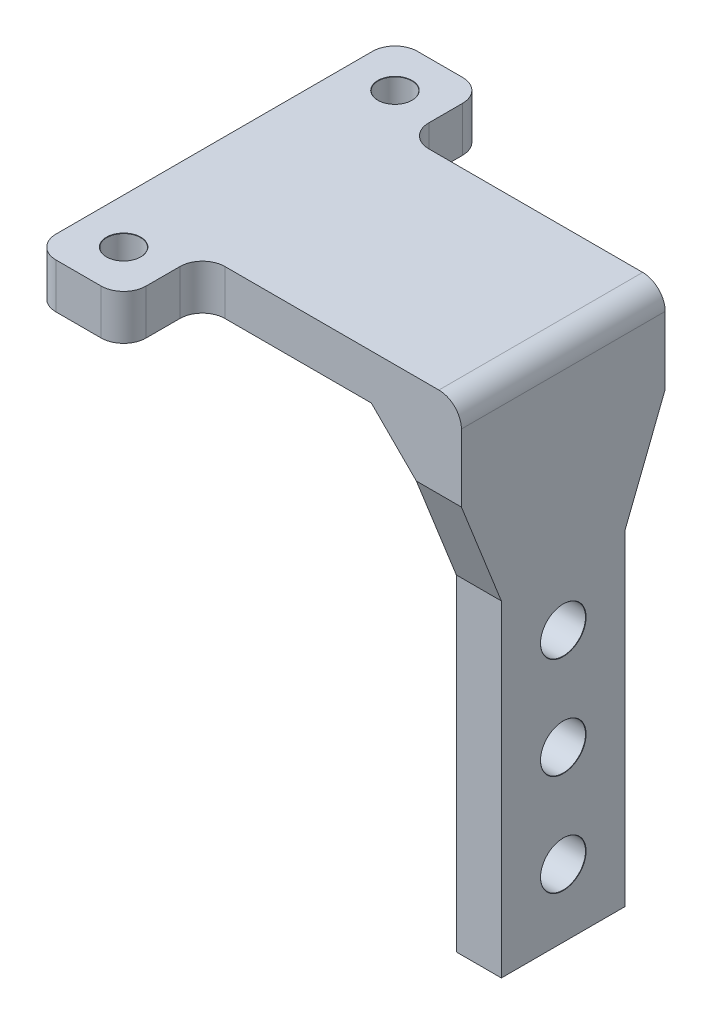
SolidWorks part; units mm, degrees
material "ABS"
ref_plane "Front Plane" through (0, 0, 0) normal (0, 0, 1) x (1, 0, 0)
ref_plane "Top Plane" through (0, 0, 0) normal (0, 1, 0) x (1, 0, 0)
ref_plane "Right Plane" through (0, 0, 0) normal (1, 0, 0) x (0, 0, -1)
sketch "Sketch1" plane through (0, 0, 0) normal (0, 1, 0) x (1, 0, 0)
  line L0 (0, 16.05) -> (0, -16.05)
  line L1 (0, -16.05) -> (8, -16.05)
  line L2 (8, -16.05) -> (8, -9.05)
  line L3 (8, -9.05) -> (31, -9.05)
  line L4 (31, -9.05) -> (31, 9.05)
  line L5 (31, 9.05) -> (8, 9.05)
  line L6 (8, 9.05) -> (8, 16.05)
  line L7 (8, 16.05) -> (0, 16.05)
  dimension "D1" = 32.1
  dimension "D2" = 8
  dimension "D3" = 7
  dimension "D4" = 23
extrude "Boss-Extrude1" add sketch "Sketch1" along normal blind 4
fillet "Fillet1" radius 2 6 edges at (0, 2, -16.05) (8, 2, -9.05) (8, 2, -16.05) (0, 2, 16.05) (8, 2, 16.05) (8, 2, 9.05)
hole_wizard "Ø3.0mm Dowel Hole1" positions "Sketch2" profile "Sketch3" hole size "Ø3.0" standard "ANSI Metric" end condition through all
sketch "Sketch2" plane through (0, 4, 0) normal (0, 1, 0) x (1, 0, 0)
  line L0 (4, 14.9464) -> (4, 9.6271) construction
  line L2 (0, 14.05) -> (0, -14.05) construction
  line L3 (8, 11.05) -> (8, 14.05) construction
  line L4 (6, 16.05) -> (2, 16.05) construction
  line L5 (2, -16.05) -> (6, -16.05) construction
  point P0 (4, 12.05)
  point P2 (4, -12.05)
  dimension "D1" = 4
  dimension "D2" = 4
sketch "Sketch3" plane through (4, 4, -12.05) normal (1, 0, 0) x (0, 0, 1)
  line L0 (0, 0) -> (0, 4)
  line L1 (0, 4) -> (1.5, 4)
  line L2 (1.5, 4) -> (1.5, 0.025)
  line L3 (1.5, 0.025) -> (1.525, 0)
  line L5 (1.525, 0) -> (0, 0)
  line L6 (-1.5, 0.025) -> (-1.525, 0) construction
  line L11 (0, -6.35) -> (0, 107.95) construction
  dimension "Thru Hole Dia." = 3
  dimension "Thru Hole Depth" = 4
  dimension "Near C'Sink Dia." = 3.05
  dimension "Near C'Sink Angle" = 90
sketch "Sketch4" plane through (0, 0, 0) normal (0, -1, 0) x (-1, 0, 0)
  line L0 (-31, 9.05) -> (-10, 9.05) construction
  line L1 (-31, -9.05) -> (-27, -9.05)
  line L2 (-31, -9.05) -> (-31, 9.05)
  line L3 (-31, 9.05) -> (-27, 9.05)
  line L4 (-27, -9.05) -> (-27, 9.05)
  dimension "D1" = 4
extrude "Boss-Extrude2" add sketch "Sketch4" along normal blind 42
chamfer "Chamfer1" distance 4 angle 45 1 edges at (27, 0, 0)
fillet "Fillet2" radius 2 1 edges at (31, 4, 0)
hole_wizard "Ø4.0mm Dowel Hole1" positions "Sketch7" profile "Sketch9" hole size "Ø4.0" standard "ANSI Metric" end condition through all
sketch "Sketch7" plane through (31, 0, 0) normal (1, 0, 0) x (0, 0, -1)
  line L0 (0, -29.3755) -> (0, -38.7068) construction
  line L2 (-9.05, 2) -> (-9.05, -42) construction
  line L3 (9.05, 2) -> (9.05, -42) construction
  line L4 (9.05, -42) -> (-9.05, -42) construction
  point P0 (0, -36)
  point P2 (0, -27)
  point P4 (0, -18)
  dimension "D1" = 6
  dimension "D2" = 9
  dimension "D3" = 9
sketch "Sketch9" plane through (31, -36, 0) normal (0, 1, 0) x (0, 0, -1)
  line L0 (0, 0) -> (0, 31)
  line L1 (0, 31) -> (2, 31)
  line L2 (2, 31) -> (2, 0.025)
  line L3 (2, 0.025) -> (2.025, 0)
  line L5 (2.025, 0) -> (0, 0)
  line L6 (-2, 0.025) -> (-2.025, 0) construction
  line L11 (0, -6.35) -> (0, 107.95) construction
  dimension "Thru Hole Dia." = 4
  dimension "Thru Hole Depth" = 31
  dimension "Near C'Sink Dia." = 4.05
  dimension "Near C'Sink Angle" = 90
sketch "Sketch11" plane through (27, 0, 0) normal (-1, 0, 0) x (0, 0, 1)
  line L0 (-9.05, -4) -> (-5.5, -13)
  line L1 (-5.5, -13) -> (-5.5, -42)
  line L2 (9.05, -42) -> (-9.05, -42) construction
  line L3 (-5.5, -37.5084) -> (-5.5, -13) construction
  line L4 (-5.5, -42) -> (-9.05, -42)
  line L5 (-9.05, -4) -> (-9.05, -42)
  line L7 (9.05, -4) -> (-9.05, -4) construction
  dimension "D1" = 9
extrude "Cut-Extrude1" cut sketch "Sketch11" against normal through all both and the other way through all
sketch "Sketch12" plane through (27, 0, 0) normal (-1, 0, 0) x (0, 0, 1)
  line L0 (9.05, -4) -> (5.5, -13)
  line L1 (5.5, -13) -> (5.5, -42)
  line L2 (9.05, -42) -> (-5.5, -42) construction
  line L3 (5.5, -42) -> (9.05, -42)
  line L4 (9.05, -42) -> (9.05, -4)
  line L5 (9.05, -4) -> (-9.05, -4) construction
  dimension "D1" = 9
  dimension "D2" = 3.55
extrude "Cut-Extrude2" cut sketch "Sketch12" against normal through all both
